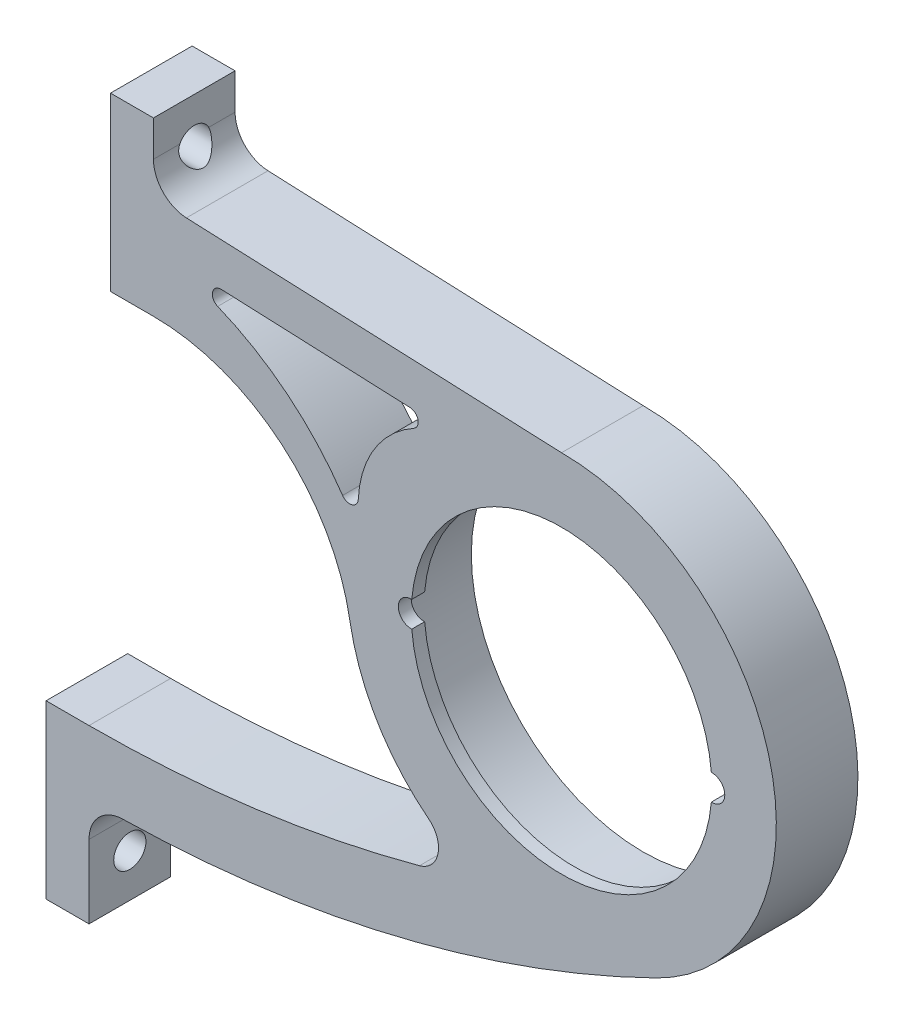
SolidWorks part; units mm, degrees
material "6061 Alloy"
ref_plane "Front Plane" through (0, 0, 0) normal (0, 0, 1) x (1, 0, 0)
ref_plane "Top Plane" through (0, 0, 0) normal (0, 1, 0) x (1, 0, 0)
ref_plane "Right Plane" through (0, 0, 0) normal (1, 0, 0) x (0, 0, -1)
sketch "Sketch1" plane through (0, 0, 0) normal (0, 0, 1) x (1, 0, 0)
  line L0 (-133.35, 88.9) -> (-133.35, 38.1)
  line L1 (-133.35, 38.1) -> (-120.65, 38.1)
  line L2 (-133.35, 88.9) -> (-120.65, 88.9)
  line L3 (-120.65, 88.9) -> (-120.65, 68.58)
  line L4 (-120.65, 68.58) -> (0, 63.5)
  line L5 (-152.4, -76.2) -> (-139.7, -76.2)
  line L6 (-152.4, -76.2) -> (-152.4, -127)
  line L7 (-152.4, -127) -> (-139.7, -127)
  line L8 (-139.7, -127) -> (-139.7, -95.25)
  line L9 (-26.7873, 51.9166) -> (-129.54, 56.2431)
  circle A1 centre (0, 0) radius 50.8
  arc A7 (27.94, -57.0229) -> (0, 63.5) centre (0, 0) ccw
  arc A13 (-139.7, -95.25) -> (27.94, -57.0229) centre (-136.9997, 279.6033) ccw
  arc A14 (-62.5737, -10.8063) -> (-25.2005, -58.2854) centre (0, 0) ccw
  arc A15 (-25.2005, -58.2854) -> (-139.7, -76.2) centre (-139.7, 298.6631) cw
  arc A16 (-62.5737, -10.8063) -> (-120.65, 38.1) centre (-120.65, -20.8359) ccw
  arc A17 (-57.4211, 7.0272) -> (-129.54, 56.2431) centre (-133.0154, -26.2976) ccw
  arc A18 (-26.7873, 51.9166) -> (-57.4211, 7.0272) centre (-28.1338, 19.9381) ccw
  dimension "D2" = 101.6
  dimension "D13" = 12.7
  dimension "D14" = 7.62
  dimension "D25" = 12.7
  dimension "D3" = 50.8
  dimension "D4" = 12.7
  dimension "D5" = 20.32
  dimension "D6" = 133.35
  dimension "D7" = 152.4
  dimension "D8" = 12.7
  dimension "D9" = 50.8
  dimension "D10" = 31.75
  dimension "D11" = 88.9
  dimension "D12" = 127
  dimension "D15" = 10.16
  dimension "D16" = 8.89
  dimension "D19" = 167.64
extrude "Boss-Extrude1" add sketch "Sketch1" along normal blind 24.13
fillet "Fillet1" radius 10.16 2 edges at (-139.7, -95.25, 12.065) (-120.65, 68.58, 12.065)
fillet "Fillet2" radius 2.54 3 edges at (-57.4211, 7.0272, 12.065) (-26.7873, 51.9166, 12.065) (-129.54, 56.2431, 12.065)
fillet "Fillet3" radius 7.62 1 edges at (-25.2005, -58.2854, 12.065)
sketch "Sketch2" plane through (-152.4, 0, 0) normal (-1, 0, 0) x (0, 0, 1)
  line L0 (24.13, 88.9) -> (0, 88.9) construction
  line L1 (24.13, -127) -> (0, -127) construction
  circle A0 centre (12.065, -114.3) radius 4.7625
  circle A1 centre (12.065, 76.2) radius 4.7625
  point P6 (12.065, 88.9)
  dimension "D1" = 9.525
  dimension "D2" = 12.7
  dimension "D3" = 12.7
extrude "Cut-Extrude1" cut sketch "Sketch2" against normal through all
sketch "Sketch3" plane through (0, 0, 24.13) normal (0, 0, 1) x (1, 0, 0)
  circle A0 centre (0, 0) radius 50.8 construction
  circle A1 centre (0, 0) radius 50.8
  arc A2 (-44.2867, -3.8065) -> (44.2867, -3.8065) centre (0, 0) ccw
  arc A3 (-44.2867, 3.8065) -> (-44.2867, -3.8065) centre (-44.45, 0) ccw
  arc A4 (44.2867, -3.8065) -> (44.2867, 3.8065) centre (44.45, 0) ccw
  arc A5 (44.2867, 3.8065) -> (-44.2867, 3.8065) centre (0, 0) ccw
  point P8 (0, 0)
  point P9 (-45.5997, 0)
  point P10 (0, 0)
  point P11 (0, 0)
  dimension "D1" = 88.9
  dimension "D2" = 2.54
  dimension "D3" = 2.54
extrude "Boss-Extrude2" add sketch "Sketch3" against normal blind 3.81
